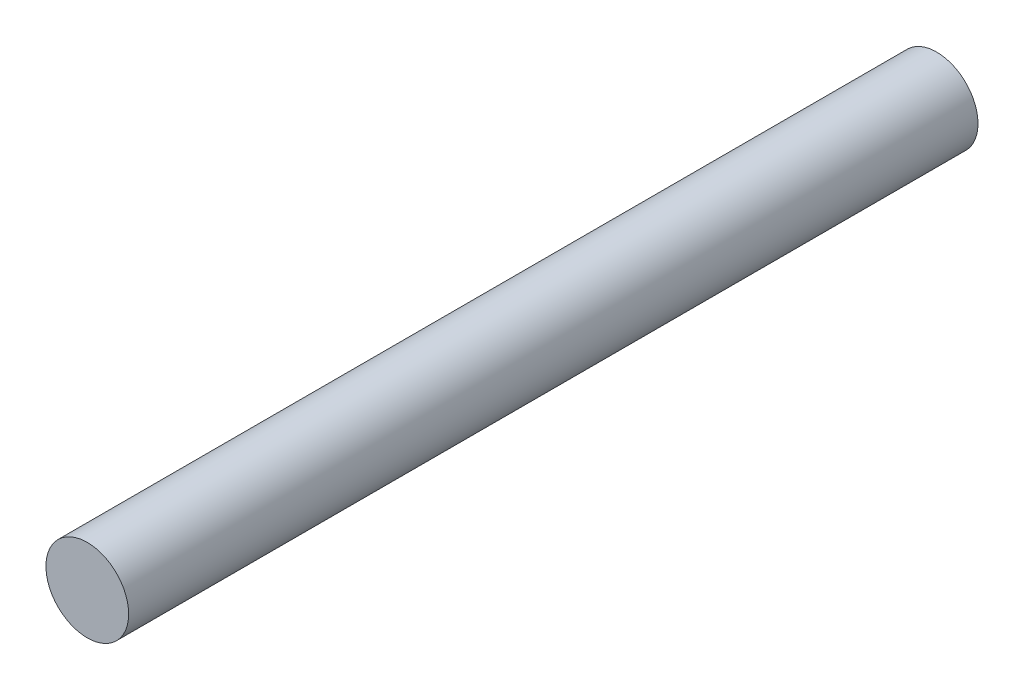
SolidWorks part; units mm, degrees
ref_plane "Front Plane" through (0, 0, 0) normal (0, 0, 1) x (1, 0, 0)
ref_plane "Top Plane" through (0, 0, 0) normal (0, 1, 0) x (1, 0, 0)
ref_plane "Right Plane" through (0, 0, 0) normal (1, 0, 0) x (0, 0, -1)
sketch "Sketch1" plane through (0, 0, 0) normal (0, 0, 1) x (1, 0, 0)
  circle A0 centre (0, 0) radius 4.6
  circle A1 centre (0, 0) radius 5.6
  dimension "D1" = 9.2
  dimension "D2" = 11.2
extrude "Boss-Extrude1" add sketch "Sketch1" along normal blind 115 contours A0 | A1 A0 region at (0, 0, 0) region at (-5.4416, 0, 0)
extrude "Cut-Extrude1" cut sketch "Sketch1<3>" along normal blind 113 contours A0 region at (0, 0, 0)
sketch "Sketch1<3>" plane through (0, 0, 0) normal (0, 0, 1) x (1, 0, 0) same geometry as "Sketch1"
ref_plane "Plane1" through (0, 0, 85) normal (0, 0, 1) x (1, 0, 0)
sketch "Sketch2" plane through (0, 0, 85) normal (0, 0, 1) x (1, 0, 0)
  line L1 (2.75, -6.3446) -> (-2.75, -6.3446)
  line L2 (2.75, -6.3446) -> (2.75, -4.8554)
  line L3 (2.75, -4.8554) -> (-2.75, -4.8554)
  line L4 (-2.75, -6.3446) -> (-2.75, -4.8554)
  line L5 (2.75, -6.3446) -> (-2.75, -4.8554) construction
  line L6 (2.75, -4.8554) -> (-2.75, -6.3446) construction
  circle A0 centre (0, 0) radius 5.6 construction
  point P0 (0, -5.6)
  dimension "D1" = 5.5
extrude "Cut-Extrude2" cut sketch "Sketch2" against normal blind 55
